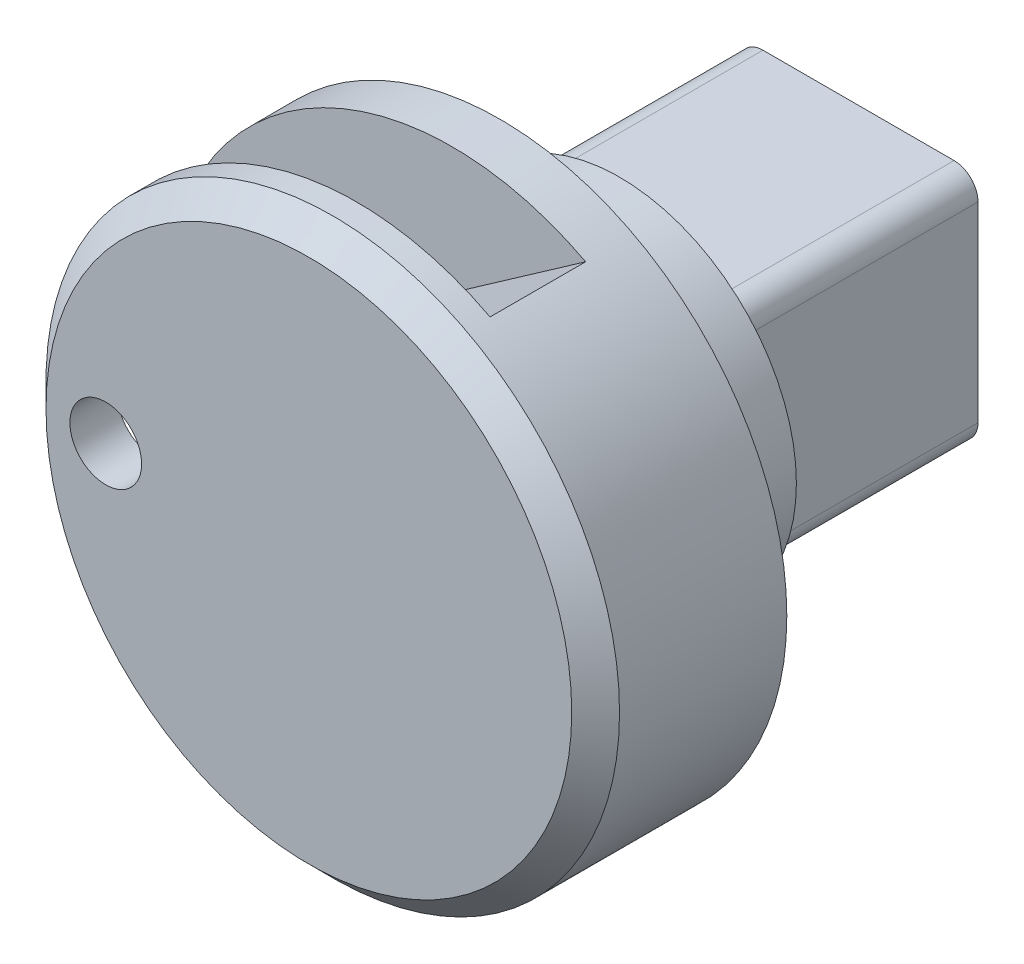
SolidWorks part; units mm, degrees
ref_plane "Front Plane" through (0, 0, 0) normal (0, 0, 1) x (1, 0, 0)
ref_plane "Top Plane" through (0, 0, 0) normal (0, 1, 0) x (1, 0, 0)
ref_plane "Right Plane" through (0, 0, 0) normal (1, 0, 0) x (0, 0, -1)
sketch "Sketch1" plane through (0, 0, 0) normal (0, 0, 1) x (1, 0, 0)
  line L1 (-5, -5) -> (5, -5)
  line L2 (-5, -5) -> (-5, 5)
  line L3 (-5, 5) -> (5, 5)
  line L4 (5, -5) -> (5, 5)
  line L5 (-5, -5) -> (5, 5) construction
  line L6 (-5, 5) -> (5, -5) construction
  circle A0 centre (0, 0) radius 7.4
  dimension "D1" = 14.8
  dimension "D3" = 10
  dimension "D4" = 10
extrude "Boss-Extrude1" add sketch "Sketch1" against normal blind 10 contours L4 L3 L2 L1
extrude "Boss-Extrude2" add sketch "Sketch1<4>" along normal blind 5 contours A0
sketch "Sketch1<4>" plane through (0, 0, 0) normal (0, 0, 1) x (1, 0, 0) same geometry as "Sketch1"
fillet "Fillet1" radius 1 4 edges at (5, 5, -5) (-5, 5, -5) (-5, -5, -5) (5, -5, -5)
sketch "Sketch2" plane through (0, 0, 0) normal (0, 0, 1) x (1, 0, 0)
  circle A0 centre (0, 0) radius 12
  dimension "D1" = 24
extrude "Boss-Extrude3" add sketch "Sketch2" along normal blind 2 from surface starting at face at (7.4, 0, 5)
sketch "Sketch3" plane through (0, 0, 0) normal (0, 0, 1) x (1, 0, 0)
  line L0 (0, 0) -> (0, 16.1137) construction
  line L1 (0, 0) -> (0, -19.6849) construction
  line L2 (0, 0) -> (-9.7508, 13.9256) construction
  line L3 (0, 0) -> (-15.2488, -18.1728) construction
  line L4 (0, 0) -> (-26.1304, 0) construction
  line L5 (-3.1547, 4.5053) -> (5.5819, 10.6227)
  line L6 (-3.5353, -4.2132) -> (4.6348, -11.0688)
  circle A0 centre (0, 0) radius 8.5 construction
  circle A1 centre (-4.8754, 6.9628) radius 3
  circle A2 centre (-5.4637, -6.5114) radius 3
  circle A3 centre (-8.5, 0) radius 1.5
  circle A4 centre (0, 0) radius 5.5
  circle A6 centre (0, 0) radius 12
  point P17 (0, 0)
  point P18 (0, 0)
  dimension "D3" = 6
  dimension "D4" = 6
  dimension "D5" = 17
  dimension "D6" = 3
  dimension "D7" = 24
  dimension "D1" = 55
  dimension "D2" = 50
extrude "Boss-Extrude4" add sketch "Sketch3" along normal blind 4 from surface contours L6 A6 L5 A4 | A4 region at (6.4077, -0.2798, 0) region at (0, 0, 0) starting at face at (12, 0, 7)
extrude "Boss-Extrude5" add sketch "Sketch3<3>" along normal blind 2 from surface contours A6 starting at face at (2.0643, -0.0901, 11)
sketch "Sketch3<3>" plane through (0, 0, 0) normal (0, 0, 1) x (1, 0, 0) same geometry as "Sketch3"
extrude "Cut-Extrude1" cut sketch "Sketch3<4>" against normal blind 7 from surface contours A3 starting at face at (12, 0, 13)
sketch "Sketch3<4>" plane through (0, 0, 0) normal (0, 0, 1) x (1, 0, 0) same geometry as "Sketch3"
chamfer "Chamfer2" distance 1 angle 45 1 edges at (12, 0, 13)
